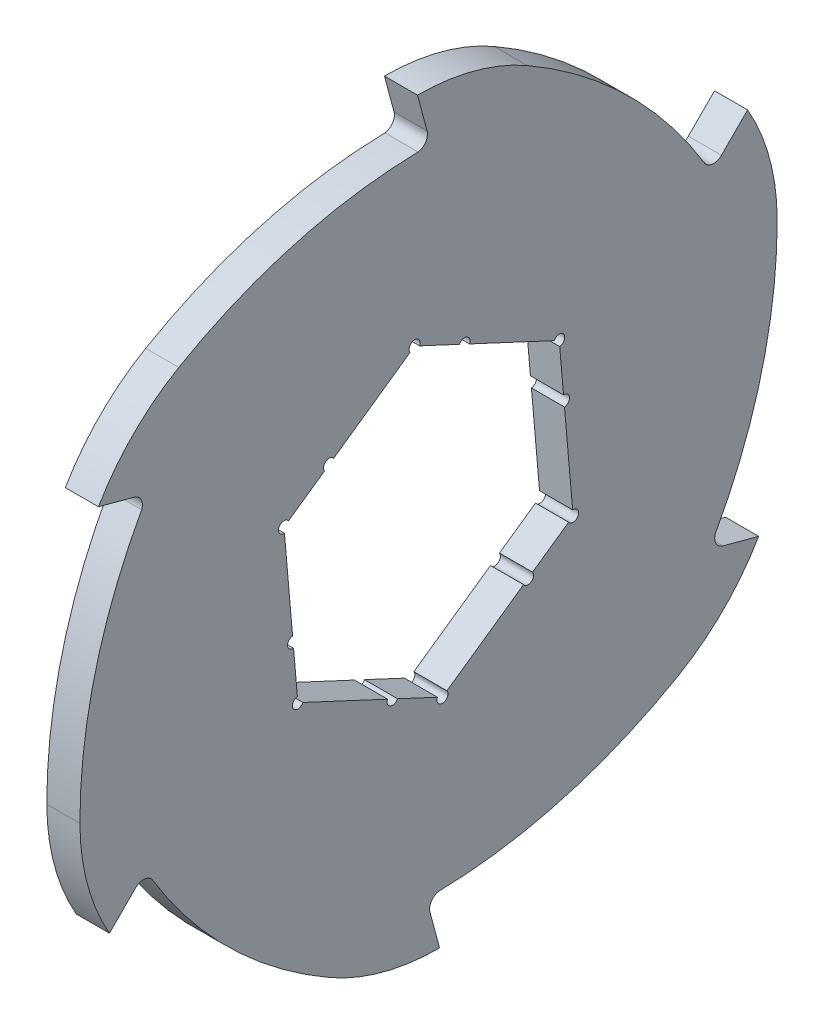
SolidWorks part; units mm, degrees
note: '?' marks a value the reader was unsure of.
material "1.0037 (S235JR)"
ref_plane "Alzado" through (0, 0, 0) normal (0, 0, 1) x (1, 0, 0)
ref_plane "Planta" through (0, 0, 0) normal (0, 1, 0) x (1, 0, 0)
ref_plane "Vista lateral" through (0, 0, 0) normal (1, 0, 0) x (0, 0, -1)
sketch "Sketch1" plane through (0, 0, 0) normal (1, 0, 0) x (0, 0, -1)
  line L0 (-56.6126, 0) -> (65.57, 0) construction
  line L1 (23.6942, 16.5908) -> (-2.521, 28.8152)
  line L2 (-2.521, 28.8152) -> (-26.2152, 12.2243)
  line L3 (-26.2152, 12.2243) -> (-23.6942, -16.5908)
  line L4 (-23.6942, -16.5908) -> (2.521, -28.8152)
  line L5 (2.521, -28.8152) -> (26.2152, -12.2243)
  line L6 (26.2152, -12.2243) -> (23.6942, 16.5908)
  circle A0 centre (0, 0) radius 25.05 construction
  circle A1 centre (0, 0) radius 59
  dimension "D2" = 118
  dimension "D1" = 50.1
  dimension "D3" = 25
extrude "Extrude1" add sketch "Sketch1" along normal mid plane 6
ref_axis "Axis1" through (-5.5, 0, 0) along (1, 0, 0)?
sketch "Sketch2" plane through (0, 0, 0) normal (1, 0, 0) x (0, 0, -1)
  line L0 (-2, 67.9618) -> (-0.2627, 61.4781)
  line L1 (0, 0) -> (0, 77.6328) construction
  line L4 (-2.1226, 58.9618) -> (0, 0) construction
  circle A0 centre (0, 0) radius 59 construction
  arc A1 (-2, 67.9618) -> (17.9271, 62.6448) centre (-2, 27.9618) cw
  arc A3 (51.2137, 29.2943) -> (-2.1226, 58.9618) centre (0, 0) ccw
  arc A4 (-0.2627, 61.4781) -> (-2.1226, 58.9618) centre (-2.1946, 60.9605) cw
  arc A5 (17.9271, 62.6448) -> (51.2137, 29.2943) centre (-26.9089, -15.3919) cw
  point P10 (-2, 67.9618)
  dimension "D2" = 40
  dimension "D4" = 2
  dimension "D3" = 9
  dimension "D6" = 90
  dimension "D1" = 15
  dimension "D5" = 2
extrude "Extrude2" add sketch "Sketch2" against normal mid plane 6
fillet "Fillet1" [suppressed] radius 0.6
pattern_circular "CirPattern1" count 6 over 360 about axis through (0, 0, 0) along (1, 0, 0) of "Extrude2", "Fillet1"
sketch "Sketch4" [suppressed] plane through (3, 0, 0) normal (1, 0, 0) x (0, 0, -1)
  circle A0 centre (0, 0) radius 67.9646 construction
  dimension "D1" = 135.9291
hole_wizard "Ø2.0 (2) Diameter Hole1" positions "Sketch5" profile "Sketch7" hole size "Ø2.0" standard "ISO" end condition up to next
sketch "Sketch5" plane through (3, 0, 0) normal (1, 0, 0) x (0, 0, -1)
  point P0 (-2.521, 28.8152)
  point P7 (23.6942, 16.5908)
  point P8 (26.2152, -12.2243)
  point P9 (2.521, -28.8152)
  point P10 (-23.6942, -16.5908)
  point P11 (-26.2152, 12.2243)
  dimension "D1" = 6
sketch "Sketch7" plane through (3, 28.8152, 2.521) normal (0, 1, 0) x (0, 0, -1)
  line L0 (0, 0) -> (0, 6)
  line L1 (0, 6) -> (1, 6)
  line L2 (1, 6) -> (1, 0)
  line L5 (1, 0) -> (0, 0)
  line L11 (0, -6.35) -> (0, 107.95) construction
  dimension "Diámetro de taladro hasta el siguiente" = 2
  dimension "Profundidad de taladro hasta el siguiente" = 6
hole_wizard "Ø2.0 (2) Diameter Hole3" positions "Sketch10" profile "Sketch11" hole size "Ø2.0" standard "ISO" end condition up to next
sketch "Sketch10" plane through (3, 0, 0) normal (1, 0, 0) x (0, 0, -1)
  line L0 (-1.6147, 28.3926) -> (6.5195, 24.5995) construction
  line L1 (22.7879, 17.0135) -> (-1.6147, 28.3926) construction
  line L2 (6.5195, 24.5995) -> (14.6537, 20.8065) construction
  line L3 (14.6537, 20.8065) -> (22.7879, 17.0135) construction
  point P2 (6.5195, 24.5995)
sketch "Sketch11" plane through (3, 24.5995, -6.5195) normal (0, 1, 0) x (0, 0, -1)
  line L0 (0, 0) -> (0, 6.001)
  line L1 (0, 6.001) -> (1, 6.001)
  line L2 (1, 6.001) -> (1, 0)
  line L5 (1, 0) -> (0, 0)
  line L11 (0, -6.35) -> (0, 107.95) construction
  dimension "Diámetro de taladro hasta el siguiente" = 2
  dimension "Profundidad de taladro hasta el siguiente" = 6.001
hole_wizard "Ø2.0 (2) Diameter Hole4" [suppressed] positions "Sketch12" profile "Sketch13" hole size "Ø2.0" standard "ISO"
sketch "Sketch12" plane through (3, 0, 0) normal (1, 0, 0) x (0, 0, -1)
  line L0 (13.4626, 25.05) -> (-3.4875, 25.05) construction
  point P0 (4.9875, 25.05)
sketch "Sketch13" plane through (3, 25.05, -4.9875) normal (0, 1, 0) x (0, 0, -1)
  line L0 (0, 0) -> (0, 6)
  line L1 (0, 6) -> (1, 6)
  line L2 (1, 6) -> (1, 0)
  line L5 (1, 0) -> (0, 0)
  line L11 (0, -6.35) -> (0, 107.95) construction
  dimension "Diámetro de taladro hasta el siguiente" = 2
  dimension "Profundidad de taladro hasta el siguiente" = 6
pattern_circular "CirPattern2" count 6 every 60 about axis through (0, 0, 0) along (1, 0, 0) of "Ø2.0 (2) Diameter Hole3"
pattern_circular "CirPattern3" [suppressed] count 1 every? 60? about axis through (-5.5, 0, 0) along (1, 0, 0)
equation "\"D1@Extrude2\"=\"D1@Extrude1\""
